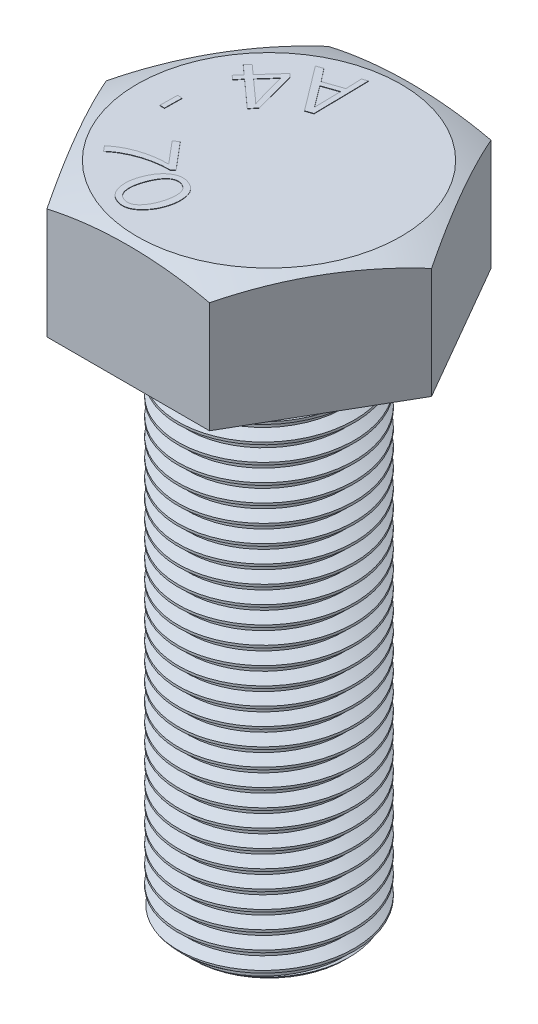
SolidWorks part; units mm, degrees
material "304 STAINLESS STEEL"
ref_plane "Front Plane" through (0, 0, 0) normal (0, 0, 1) x (1, 0, 0)
ref_plane "Top Plane" through (0, 0, 0) normal (0, 1, 0) x (1, 0, 0)
ref_plane "Right Plane" through (0, 0, 0) normal (1, 0, 0) x (0, 0, -1)
ref_axis "X-Axis" through (-88.99, 0, 0) along (1, 0, 0)
ref_axis "Y-Axis" through (0, 55, 0) along (0, -1, 0)
ref_axis "Z-Axis" through (0, 0, -88.99) along (0, 0, 1)
sketch "Sketch1" plane through (0, 0, 0) normal (0, 1, 0) x (1, 0, 0)
  line L1 (2.3094, -4) -> (4.6188, 0)
  line L2 (4.6188, 0) -> (2.3094, 4)
  line L3 (2.3094, 4) -> (-2.3094, 4)
  line L4 (-2.3094, 4) -> (-4.6188, 0)
  line L5 (-4.6188, 0) -> (-2.3094, -4)
  line L6 (-2.3094, -4) -> (2.3094, -4)
  circle A0 centre (0, 0) radius 4 construction
  dimension "D1" = 8
extrude "Boss-Extrude1" add sketch "Sketch1" against normal blind 3.5 and the other way blind 0.0001
sketch "Sketch2" plane through (0, 0, 0) normal (0, 0, 1) x (1, 0, 0)
  line L0 (2.3094, 0.0001) -> (4.6188, 0.0001) construction
  line L1 (4.6188, -3.5) -> (4.6188, 0.0001) construction
  line L2 (3.75, 0.0001) -> (4.6188, 0.0001)
  line L3 (4.6188, 0.0001) -> (4.6188, -0.3499)
  arc A0 (3.75, 0.0001) -> (4.6188, -0.3499) centre (0.4518, -9.4403) cw
  dimension "D3" = 10
  dimension "D1" = 0.35
  dimension "D2" = 3.75
revolve "Cut-Revolve1" cut sketch "Sketch2" angle 360 about axis through (0, 55, 0) along (0, -1, 0)
sketch "Sketch3" plane through (0, -3.5, 0) normal (0, -1, 0) x (1, 0, 0)
  line L0 (-12.2928, 3.8) -> (12.57, 3.8) construction
  line L1 (-2.3094, 4) -> (2.3094, 4) construction
  circle A0 centre (0, 0) radius 3.8
  dimension "D1" = 0.2
extrude "Boss-Extrude2" add sketch "Sketch3" along normal blind 0.1
sketch "Sketch4" plane through (0, -3.6, 0) normal (0, -1, 0) x (1, 0, 0)
  circle A0 centre (0, 0) radius 2.5
  dimension "D1" = 5
extrude "Boss-Extrude3" add sketch "Sketch4" along normal blind 1
fillet "Fillet1" radius 0.5 1 edges at (0, -3.6, -2.5)
sketch "Sketch5" plane through (0, -4.6, 0) normal (0, -1, 0) x (1, 0, 0)
  circle A1 centre (0, 0) radius 2.5
  circle A2 centre (0, 0) radius 2.5
  dimension "D1" = 0
extrude "Boss-Extrude4" add sketch "Sketch5" along normal blind 14 separate body
thread "Thread1" pitch 0.5 method cut profile "Thread Profile1" start angle 0, offset 5, length 0, pitch 0.5, diameter 5
ref_plane "Plane1" through (2.5, -23.6, 0) normal (0, 0, 1) x (1, 0, 0)
sketch "Thread Profile1" plane through (2.5, -23.6, 0) normal (0, 0, 1) x (1, 0, 0)
  line L0 (0, 0) -> (0, 0.5) construction
  line L11 (0, 0) -> (0, 0.4333)
  line L12 (0, 0.4333) -> (-0.28, 0.2717)
  line L13 (-0.28, 0.2717) -> (-0.28, 0.1617)
  line L15 (-0.28, 0.1617) -> (0, 0)
  line L17 (-0.28, 0.2167) -> (0, 0.2167) construction
  point P2 (0, 0)
  dimension "Pitch" = 0.5
  dimension "Profile_Angle" = 60
  dimension "Profile_Land" = 0.11
  dimension "Profile_Height" = 0.28
sketch "Sketch11" plane through (0, 0, 0) normal (0, 0, 1) x (1, 0, 0)
  line L0 (2.5, -18.25) -> (2.15, -18.6)
  line L1 (2.15, -18.6) -> (2.5, -18.6)
  line L2 (2.5, -18.6) -> (2.5, -18.25)
  line L3 (-0.9766, -18.6) -> (2.5, -18.6) construction
  line L4 (2.5, -4.6) -> (2.5, -4.1) construction
  dimension "D1" = 0.35
  dimension "D2" = 45
revolve "Cut-Revolve2" cut sketch "Sketch11" angle 360 about axis through (0, 55, 0) along (0, -1, 0)
sketch "Sketch19" plane through (0, 0.0001, 0) normal (0, 1, 0) x (1, 0, 0)
  circle A0 centre (0, 0) radius 3.4 construction
  circle A1 centre (0, 0) radius 3.75 construction
  text T0 "A4 - 70" font "Segoe UI" height 1.5
  dimension "D1" = 0.35
extrude "Boss-Extrude7" add sketch "Sketch19" along normal blind 0.01
